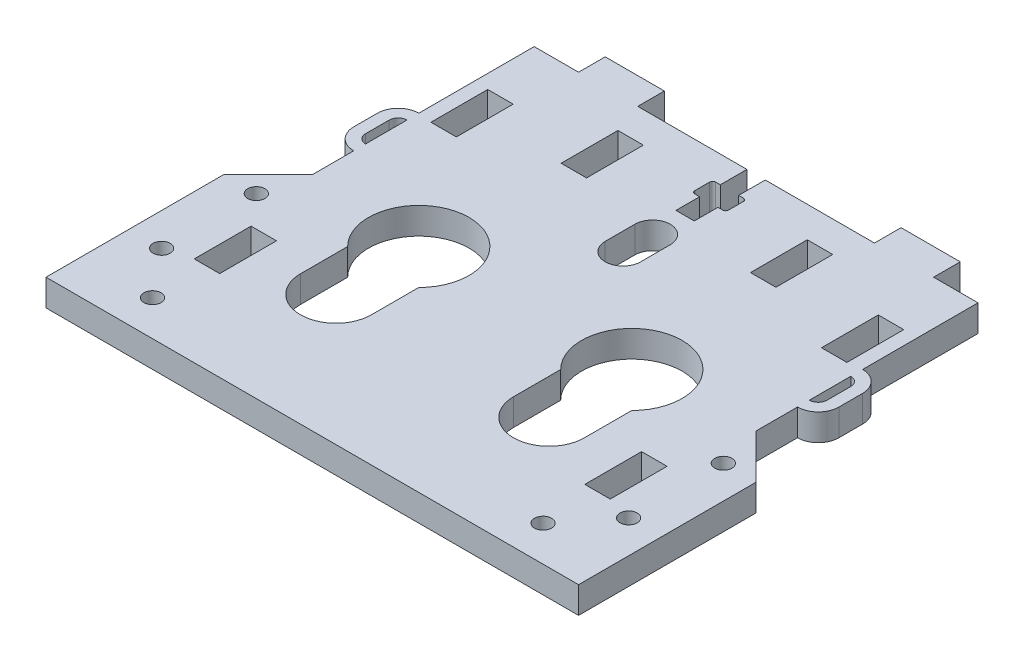
SolidWorks part; units mm, degrees
ref_plane "Front Plane" through (0, 0, 0) normal (0, 0, 1) x (1, 0, 0)
ref_plane "Top Plane" through (0, 0, 0) normal (0, 1, 0) x (1, 0, 0)
ref_plane "Right Plane" through (0, 0, 0) normal (1, 0, 0) x (0, 0, -1)
sketch "Sketch1" plane through (0, 0, 0) normal (0, 1, 0) x (1, 0, 0)
  line L1 (-37.5, 37.5) -> (37.5, 37.5)
  line L2 (-37.5, 37.5) -> (-37.5, -37.5)
  line L3 (-37.5, -37.5) -> (37.5, -37.5)
  line L4 (37.5, 37.5) -> (37.5, -37.5)
  line L5 (-37.5, 37.5) -> (37.5, -37.5) construction
  line L6 (-37.5, -37.5) -> (37.5, 37.5) construction
  point P0 (0, 0)
  dimension "D1" = 75
  dimension "D2" = 75
extrude "MainShape" add sketch "Sketch1" along normal blind 4.5
sketch "Sketch2" plane through (0, 4.5, 0) normal (0, 1, 0) x (1, 0, 0)
  line L0 (0, -37.5) -> (0, 37.5) construction
  line L1 (-37.5, -37.5) -> (37.5, -37.5) construction
  line L2 (37.5, 37.5) -> (-37.5, 37.5) construction
  line L4 (-5, 42) -> (5, 42)
  line L5 (-5, 42) -> (-5, 33)
  line L6 (-5, 33) -> (5, 33)
  line L7 (5, 42) -> (5, 33)
  line L8 (-5, 42) -> (5, 33) construction
  line L9 (-5, 33) -> (5, 42) construction
  dimension "D1" = 10
  dimension "D2" = 4.5
extrude "Tab1" [suppressed] add sketch "Sketch2" against normal through all
sketch "Sketch4" [suppressed] plane through (0, 4.5, 0) normal (0, 1, 0) x (1, 0, 0)
  line L0 (0, 42) -> (0, -37.5) construction
  line L1 (5, 42) -> (-5, 42) construction
  line L2 (-47.5, -37.5) -> (47.5, -37.5) construction
  line L3 (-40, 37.5) -> (-40, 27) construction
  line L4 (-5, 37.5) -> (-47.5, 37.5) construction
  line L5 (-38.25, 27) -> (-41.75, 27) construction
  line L6 (-41.75, 27) -> (-41.75, 37.5) construction
  line L7 (-38.25, 27) -> (-41.75, 27)
  line L8 (-41.75, 27) -> (-41.75, 29.5)
  line L9 (-41.75, 29.5) -> (-42.75, 29.5)
  line L10 (-43, 29.75) -> (-43, 33.45)
  line L11 (-42.75, 33.7) -> (-41.75, 33.7)
  line L12 (-41.75, 33.7) -> (-41.75, 37.5)
  line L13 (-41.75, 37.5) -> (-38.25, 37.5)
  line L14 (-38.25, 27) -> (-38.25, 37.5) construction
  line L15 (-38.25, 33.7) -> (-38.25, 37.5)
  line L16 (-37.25, 33.7) -> (-38.25, 33.7)
  line L17 (-37, 29.75) -> (-37, 33.45)
  line L18 (-38.25, 29.5) -> (-37.25, 29.5)
  line L19 (-38.25, 27) -> (-38.25, 29.5)
  line L20 (38.25, 27) -> (38.25, 37.5) construction
  line L21 (41.75, 27) -> (41.75, 37.5) construction
  line L22 (38.25, 27) -> (41.75, 27) construction
  line L23 (40, 37.5) -> (40, 27) construction
  line L24 (38.25, 27) -> (38.25, 29.5)
  line L25 (38.25, 29.5) -> (37.25, 29.5)
  line L26 (37, 29.75) -> (37, 33.45)
  line L27 (37.25, 33.7) -> (38.25, 33.7)
  line L28 (38.25, 33.7) -> (38.25, 37.5)
  line L29 (41.75, 37.5) -> (38.25, 37.5)
  line L30 (41.75, 33.7) -> (41.75, 37.5)
  line L31 (42.75, 33.7) -> (41.75, 33.7)
  line L32 (43, 29.75) -> (43, 33.45)
  line L33 (41.75, 29.5) -> (42.75, 29.5)
  line L34 (41.75, 27) -> (41.75, 29.5)
  line L35 (38.25, 27) -> (41.75, 27)
  arc A0 (-42.75, 29.5) -> (-43, 29.75) centre (-42.75, 29.75) cw
  arc A1 (-37, 29.75) -> (-37.25, 29.5) centre (-37.25, 29.75) cw
  arc A2 (-37.25, 33.7) -> (-37, 33.45) centre (-37.25, 33.45) cw
  arc A3 (-43, 33.45) -> (-42.75, 33.7) centre (-42.75, 33.45) cw
  arc A4 (43, 33.45) -> (42.75, 33.7) centre (42.75, 33.45) ccw
  arc A5 (37.25, 33.7) -> (37, 33.45) centre (37.25, 33.45) ccw
  arc A6 (37, 29.75) -> (37.25, 29.5) centre (37.25, 29.75) ccw
  arc A7 (42.75, 29.5) -> (43, 29.75) centre (42.75, 29.75) ccw
  point P24 (-43, 29.5)
  point P27 (-37, 29.5)
  point P30 (-37, 33.7)
  point P33 (-43, 33.7)
  point P56 (43, 33.7)
  point P57 (37, 33.7)
  point P58 (37, 29.5)
  point P59 (43, 29.5)
  dimension "D7" = 0.5
  dimension "D1" = 11
  dimension "D2" = 1.55
  dimension "D3" = 3.5
  dimension "D4" = 2.85
  dimension "D5" = 8
  dimension "D6" = 40
extrude "Cut-Extrude2" [suppressed] cut sketch "Sketch4" against normal through all
sketch "Sketch5" plane through (0, 4.5, 0) normal (0, 1, 0) x (1, 0, 0)
  line L0 (0, -37.5) -> (0, 37.5) construction
  line L1 (-37.5, -37.5) -> (37.5, -37.5) construction
  line L3 (33, 37.5) -> (33, -37.5) construction
  line L4 (37.5, 37.5) -> (-37.5, 37.5) construction
  line L5 (-33, 37.5) -> (-33, -37.5) construction
  line L6 (30.85, 27.3) -> (35.15, 27.3)
  line L7 (30.85, 27.3) -> (30.85, 17.7)
  line L8 (30.85, 17.7) -> (35.15, 17.7)
  line L9 (35.15, 27.3) -> (35.15, 17.7)
  line L10 (30.85, 27.3) -> (35.15, 17.7) construction
  line L11 (30.85, 17.7) -> (35.15, 27.3) construction
  line L12 (-30.85, 17.7) -> (-35.15, 27.3) construction
  line L13 (-30.85, 27.3) -> (-35.15, 17.7) construction
  line L14 (-35.15, 27.3) -> (-35.15, 17.7)
  line L15 (-30.85, 17.7) -> (-35.15, 17.7)
  line L16 (-30.85, 27.3) -> (-30.85, 17.7)
  line L17 (-30.85, 27.3) -> (-35.15, 27.3)
  line L18 (-37.5, 2.5) -> (37.5, 2.5) construction
  line L19 (-37.5, 37.5) -> (-37.5, -37.5) construction
  line L20 (37.5, -37.5) -> (37.5, 37.5) construction
  line L21 (-30.85, -22.3) -> (-35.15, -12.7) construction
  line L22 (-30.85, -12.7) -> (-35.15, -22.3) construction
  line L23 (30.85, -12.7) -> (35.15, -22.3) construction
  line L24 (30.85, -22.3) -> (35.15, -12.7) construction
  line L25 (-30.85, -22.3) -> (-35.15, -22.3)
  line L26 (-30.85, -22.3) -> (-30.85, -12.7)
  line L27 (-30.85, -12.7) -> (-35.15, -12.7)
  line L28 (-35.15, -22.3) -> (-35.15, -12.7)
  line L29 (35.15, -22.3) -> (35.15, -12.7)
  line L30 (30.85, -12.7) -> (35.15, -12.7)
  line L31 (30.85, -22.3) -> (30.85, -12.7)
  line L32 (30.85, -22.3) -> (35.15, -22.3)
  line L33 (-30.85, 27.3) -> (-35.15, 17.7) construction
  line L34 (-37.5, 37.5) -> (37.5, 37.5) construction
  line L35 (37.5, 37.5) -> (-37.5, 37.5) construction
  point P10 (33, 22.5)
  point P21 (-33, 22.5)
  point P36 (-33, -17.5)
  point P37 (33, -17.5)
  dimension "D1" = 33
  dimension "D2" = 9.6
  dimension "D3" = 4.3
  dimension "D4" = 15
  dimension "D5" = 40
extrude "Cut-Extrude3" cut sketch "Sketch5" against normal through all
sketch "Sketch6" plane through (0, 4.5, 0) normal (0, 1, 0) x (1, 0, 0)
  line L0 (-18, -37.5) -> (-18, 28) construction
  line L1 (-24, -15.5) -> (-24, -7.5208)
  line L3 (-37.5, -15.5) -> (37.5, -15.5) construction
  line L4 (-37.5, 37.5) -> (-37.5, -37.5) construction
  line L5 (37.5, -37.5) -> (37.5, 37.5) construction
  line L6 (37.5, 37.5) -> (-37.5, 37.5) construction
  line L7 (-37.5, -37.5) -> (37.5, -37.5) construction
  line L8 (-12, -15.5) -> (-12, -7.5208)
  line L9 (-37.5, 37.5) -> (37.5, 37.5) construction
  arc A0 (-24, -15.5) -> (-12, -15.5) centre (-18, -15.5) ccw
  arc A2 (-12, -7.5208) -> (-24, -7.5208) centre (-18, -1.5) ccw
  dimension "D1" = 12
  dimension "D6" = 8.5
  dimension "D2" = 53
  dimension "D3" = 0
  dimension "D5" = 0
  dimension "D7" = 14
  dimension "D4" = 18
extrude "Cut-Extrude4" cut sketch "Sketch6" against normal through all
sketch "Sketch13" plane through (0, 4.5, 0) normal (0, 1, 0) x (1, 0, 0)
  line L0 (-37.5, 0) -> (-45, -7.5)
  line L1 (-37.5, 37.5) -> (-37.5, -37.5) construction
  line L2 (-45, -7.5) -> (-45, -37.5)
  line L3 (-45, -37.5) -> (-37.5, -37.5)
  line L4 (-37.5, -37.5) -> (-37.5, 0)
  line L5 (0, 37.5) -> (0, -37.5) construction
  line L6 (37.5, 37.5) -> (-37.5, 37.5) construction
  line L7 (-37.5, -37.5) -> (37.5, -37.5) construction
  line L8 (37.5, -37.5) -> (37.5, 0)
  line L9 (45, -37.5) -> (37.5, -37.5)
  line L10 (45, -7.5) -> (45, -37.5)
  line L11 (37.5, 0) -> (45, -7.5)
  line L12 (-37.5, -37.5) -> (-37.5, 0)
  line M23 (37.5, -37.5) -> (37.5, 37.5)
  line M25 (-37.5, 37.5) -> (-37.5, -37.5)
  dimension "D1" = 45
  dimension "D2" = 30
extrude "Boss-Extrude2" add sketch "Sketch13" against normal through all contours L2 L3 L0 M25 | L11 L9 L10 M23 region at (-41.1111, 4.5, 20.5556) region at (41.1111, 4.5, 20.5556)
sketch "Sketch8" plane through (0, 4.5, 0) normal (0, 1, 0) x (1, 0, 0)
  line L0 (-18, -9.5) -> (-18, -21.5) construction
  line L1 (-18, -15.5) -> (-39.46, -15.5) construction
  line L2 (-39.46, -23.5) -> (-39.46, -7.5) construction
  line L3 (-18, -21.5) -> (-18, -9.5) construction
  circle A0 centre (-39.46, -7.5) radius 1.45
  circle A1 centre (-18, -15.5) radius 6 construction
  circle A2 centre (-39.46, -23.5) radius 1.45
  dimension "D3" = 2.9
  dimension "D1" = 0
  dimension "D2" = 8
  dimension "D4" = 21.46
extrude "Cut-Extrude6" cut sketch "Sketch8" against normal through all
mirror "Mirror1" about plane through (0, 0, 0) normal (1, 0, 0) of "Cut-Extrude6", "Cut-Extrude4"
sketch "Sketch11" plane through (0, 4.5, 0) normal (0, 1, 0) x (1, 0, 0)
  line L0 (0, 37.5) -> (0, -37.5) construction
  line L1 (37.5, 37.5) -> (-37.5, 37.5) construction
  line L2 (-45, -37.5) -> (45, -37.5) construction
  line L3 (-25, 42) -> (-25, 37.5) construction
  line L4 (-30, 37.5) -> (-20, 37.5)
  line L5 (-30, 37.5) -> (-30, 42)
  line L6 (-30, 42) -> (-20, 42)
  line L7 (-20, 37.5) -> (-20, 42)
  line L8 (25, 42) -> (25, 37.5) construction
  line L9 (20, 37.5) -> (20, 42)
  line L10 (30, 42) -> (20, 42)
  line L11 (30, 37.5) -> (30, 42)
  line L12 (30, 37.5) -> (20, 37.5)
  dimension "D1" = 10
  dimension "D2" = 4.5
  dimension "D3" = 25
extrude "RearTabs" add sketch "Sketch11" against normal through all
sketch "Sketch12" plane through (0, 4.5, 0) normal (0, 1, 0) x (1, 0, 0)
  line L0 (0, 0) -> (0, 37.5) construction
  line L1 (20, 37.5) -> (-20, 37.5) construction
  line L2 (1.55, 37.5) -> (-1.55, 37.5)
  line L3 (-1.55, 37.5) -> (-1.55, 33)
  line L4 (-1.55, 33) -> (-2.35, 33)
  line L5 (-2.85, 32.5) -> (-2.85, 30)
  line L6 (-2.35, 29.5) -> (-1.55, 29.5)
  line L7 (-1.55, 29.5) -> (-1.55, 25.5)
  line L8 (-1.55, 25.5) -> (1.55, 25.5)
  line L9 (1.55, 29.5) -> (1.55, 25.5)
  line L10 (2.35, 29.5) -> (1.55, 29.5)
  line L11 (2.85, 32.5) -> (2.85, 30)
  line L12 (1.55, 33) -> (2.35, 33)
  line L13 (1.55, 37.5) -> (1.55, 33)
  arc A0 (-2.85, 30) -> (-2.35, 29.5) centre (-2.35, 30) ccw
  arc A1 (-2.35, 33) -> (-2.85, 32.5) centre (-2.35, 32.5) ccw
  arc A2 (2.35, 33) -> (2.85, 32.5) centre (2.35, 32.5) cw
  arc A3 (2.85, 30) -> (2.35, 29.5) centre (2.35, 30) cw
  point P14 (-2.85, 29.5)
  point P17 (-2.85, 33)
  point P25 (0, 25.5)
  point P28 (2.85, 33)
  point P29 (2.85, 29.5)
  dimension "D5" = 8
  dimension "D1" = 12
  dimension "D6" = 0.5
  dimension "D2" = 3.5
  dimension "D3" = 2.85
  dimension "D4" = 1.55
extrude "FrontScrewSlot" cut sketch "Sketch12" against normal through all
sketch "Sketch14" plane through (0, 4.5, 0) normal (0, 1, 0) x (1, 0, 0)
  line L0 (-33, 27.3) -> (-33, -37.5) construction
  line L1 (-30.85, 27.3) -> (-35.15, 27.3) construction
  line L2 (-45, -37.5) -> (45, -37.5) construction
  line L3 (-30, 37.5) -> (-37.5, 37.5) construction
  line L4 (0, 0) -> (0, -37.5) construction
  line L5 (33, 27.3) -> (33, -37.5) construction
  line L6 (-33, 27.3) -> (-33, -37.5) construction
  circle A0 centre (-33, -31.5) radius 1.45
  circle A1 centre (33, -31.5) radius 1.45
  dimension "D2" = 2.9
  dimension "D1" = 69
extrude "BraceScrews" cut sketch "Sketch14" against normal through all
sketch "Sketch15" plane through (0, 4.5, 0) normal (0, 1, 0) x (1, 0, 0)
  line L0 (0, -37.5) -> (0, 25.5) construction
  line L1 (-45, -37.5) -> (45, -37.5) construction
  line L2 (-1.55, 25.5) -> (1.55, 25.5) construction
  line L3 (16, 27.5) -> (-16, 27.5) construction
  line L4 (-1.55, 37.5) -> (-20, 37.5) construction
  line L5 (-18.15, 32.3) -> (-13.85, 32.3)
  line L6 (-18.15, 32.3) -> (-18.15, 22.7)
  line L7 (-18.15, 22.7) -> (-13.85, 22.7)
  line L8 (-13.85, 32.3) -> (-13.85, 22.7)
  line L9 (-18.15, 32.3) -> (-13.85, 22.7) construction
  line L10 (-18.15, 22.7) -> (-13.85, 32.3) construction
  line L11 (18.15, 22.7) -> (13.85, 32.3) construction
  line L12 (18.15, 32.3) -> (13.85, 22.7) construction
  line L13 (13.85, 32.3) -> (13.85, 22.7)
  line L14 (18.15, 22.7) -> (13.85, 22.7)
  line L15 (18.15, 32.3) -> (18.15, 22.7)
  line L16 (18.15, 32.3) -> (13.85, 32.3)
  point P19 (0, 27.5)
  dimension "D1" = 16
  dimension "D2" = 4.3
  dimension "D3" = 9.6
  dimension "D4" = 10
extrude "FanTabs" cut sketch "Sketch15" against normal through all
sketch "Sketch16" plane through (0, 4.5, 0) normal (0, 1, 0) x (1, 0, 0)
  line L0 (0, 0) -> (0, 25.5) construction
  line L1 (-1.55, 25.5) -> (1.55, 25.5) construction
  line L2 (0, 20) -> (0, 15) construction
  line L3 (3, 20) -> (3, 15)
  line L4 (-3, 20) -> (-3, 15)
  arc A0 (3, 20) -> (-3, 20) centre (0, 20) ccw
  arc A1 (-3, 15) -> (3, 15) centre (0, 15) ccw
  point P7 (0, 17.5)
  dimension "D1" = 3
  dimension "D2" = 20
  dimension "D3" = 5
extrude "WiringSlot" cut sketch "Sketch16" against normal through all
sketch "Sketch17" plane through (0, 4.5, 0) normal (0, 1, 0) x (1, 0, 0)
  line L0 (-37.5, 14.5) -> (-37.5, 10.5) construction
  line L3 (-37.5, 37.5) -> (-37.5, 0) construction
  line L4 (-36, 14.5) -> (-36, 10.5)
  line L5 (-39, 14.5) -> (-39, 10.5)
  line L6 (-37.5, 14.5) -> (-37.5, 10.5) construction
  line L7 (-34, 14.5) -> (-34, 10.5)
  line L8 (-41, 14.5) -> (-41, 10.5)
  line L9 (-41, 12.5) -> (-37.5, 12.5) construction
  line L10 (0, 0) -> (0, -12.1805) construction
  arc A0 (-36, 14.5) -> (-39, 14.5) centre (-37.5, 14.5) ccw
  arc A1 (-39, 10.5) -> (-36, 10.5) centre (-37.5, 10.5) ccw
  arc A2 (-34, 14.5) -> (-41, 14.5) centre (-37.5, 14.5) ccw
  arc A3 (-41, 10.5) -> (-34, 10.5) centre (-37.5, 10.5) ccw
  point P4 (-37.5, 12.5)
  point P10 (-37.5, 12.5)
  dimension "D4" = 4
  dimension "D5" = 25
  dimension "D1" = 0
  dimension "D2" = 2
  dimension "D3" = 1.5
extrude "Boss-Extrude3" add sketch "Sketch17" against normal through all
mirror "Mirror2" about plane through (0, 0, 0) normal (1, 0, 0) of "Boss-Extrude3"
equation "\"X-ROD-SPACING\"=45"
equation "\"Y-ROD-SPACING\"=75"
equation "\"Z-ROD-SPACING\"=17.5"
equation "\"Y-BED-OFFSET\"=2"
equation "\"Y-BED-ROD-INSET\"=3.5"
equation "\"Y-BED-SCREW-SPACING\"=209"
equation "\"Y-BED-SCREW-CUTOUT-SLOT-HEIGHT\"=2"
equation "\"T-SLOT-NUT-FILLET-RADIUS\"=0.5"
equation "\"T-SLOT-SCREW-SHAFT-RADIUS\"=1.55"
equation "\"T-SLOT-SCREW-SHAFT-CUTOUT-LENGTH\"=11.0"
equation "\"T-SLOT-NUT-DEPTH\"=3.5"
equation "\"T-SLOT-NUT-WIDTH\"=2.85"
equation "\"T-SLOT-NUT-END-DISTANCE\"=8"
equation "\"ACRYLIC-THICKNESS\"=10"
equation "\"ACRYLIC-THICKNESS2\"=4.5"
equation "\"ACRYLIC-TAB-CUTOUT-SIZE\"=\"ACRYLIC-THICKNESS\"+\"ACRYLIC-TAB-TOLERANCE\"*2"
equation "\"ACRYLIC-TAB-WIDTH\"=\"ACRYLIC-THICKNESS\""
equation "\"ACRYLIC-M3-HOLE\"=2.9"
equation "\"SMOOTHROD-CAP-SCREW-DISTANCE\"=20"
equation "\"FRAME-WIDTH-INNER\"=370"
equation "\"NEMA17-HOLE-SPACING\"=31"
equation "\"NEMA17-CENTRAL-CUTOUT\"=22.5"
equation "\"Z-BRACKET-REACH\"=55"
equation "\"Z-ROD-INSET\"=16"
equation "\"TOP-BRACKET-SPACING\"=40"
equation "\"SMOOTHROD-X-LENGTH\"=350"
equation "\"SMOOTHROD-Y-LENGTH\"=350"
equation "\"SMOOTHROD-Z-LENGTH\"=350"
equation "\"SMOOTHROD-TIGHTENING-HEADROOM\"=.25"
equation "\"LEADSCREW-Z-LENGTH\"=300"
equation "\"SCREW-LENGTH-FRAME\"=\"ACRYLIC-THICKNESS\" + 10"
equation "\"SCREW-LENGTH-MOTOR\"=\"ACRYLIC-THICKNESS\" + 5"
equation "\"SCREW-LENGTH-EXTRUDER\"=28"
equation "\"SCREW-HEAD-RADIUS\"=6"
equation "\"PRINTED-X-SMOOTHROD-DIAMETER\"=9.0"
equation "\"PRINTED-X-SMOOTHROD-CUTOUT\"=10"
equation "\"PRINTED-X-BASE-HEIGHT\"=10"
equation "\"PRINTED-LM8UU-CUTOUT-SIZE\"=15.5"
equation "\"PRINTED-LM8UU-CUTOUT-LENGTH\"=24.5"
equation "\"PRINTED-X-IDLER-HEIGHT\"=16"
equation "\"PSU-MOUNTING-WIDTH\"=95"
equation "\"PSU-MOUNTING-HEIGHT\"=177"
equation "\"Y-BELT-TO-ROD-DISTANCE\"=20"
equation "\"SPOOL-HOLDER-ROD-SPACING\"=150"
equation "\"ACRYLIC-X-CARRIAGE-WIDTH\"=55"
equation "\"ACRYLIC-X-CARRIAGE-HEIGHT\"=75"
equation "\"ACRYLIC-X-CARRIAGE-SCREW-SPACING-X\"=15"
equation "\"ACRYLIC-X-CARRIAGE-SCREW-SPACING-Y\"=33"
equation "\"ACRYLIC-X-CARRIAGE-CENTER-TAB-SPACING\"=14"
equation "\"D1@MainShape\" = \"ACRYLIC-THICKNESS2\""
equation "\"D1@Sketch2\"=\"ACRYLIC-TAB-WIDTH\""
equation "\"D2@Sketch2\"=\"ACRYLIC-THICKNESS2\""
equation "\"D1@Sketch4\"=\"T-SLOT-SCREW-SHAFT-CUTOUT-LENGTH\""
equation "\"D2@Sketch4\"=\"T-SLOT-SCREW-SHAFT-RADIUS\""
equation "\"D3@Sketch4\"=\"T-SLOT-NUT-DEPTH\""
equation "\"D4@Sketch4\"=\"T-SLOT-NUT-WIDTH\""
equation "\"D5@Sketch4\"=\"T-SLOT-NUT-END-DISTANCE\""
equation "\"D7@Sketch4\"=\"T-SLOT-NUT-FILLET-RADIUS\""
equation "\"ACRYLIC-X-CARRIAGE-EXTRUDER-SHELF-DEPTH\"=\"ACRYLIC-X-CARRIAGE-EXTRUDER-OFFSET\" + 28"
equation "\"ACRYLIC-X-CARRIAGE-LM8UU-CUTOUT-WIDTH\"=24.25"
equation "\"ACRYLIC-X-CARRIAGE-EXTRUDER-BRACE-SPACING\"=23"
equation "\"ACRYLIC-X-CARRIAGE-EXTRUDER-BRACE-TAB-OFFSET\"=20"
equation "\"ACRYLIC-X-CARRIAGE-EXTRUDER-BRACE-HEIGHT\"=35"
equation "\"ACRYLIC-X-CARRIAGE-EXTRUDER-BRACE-SCREW-SPACING\"=22"
equation "\"D2@Sketch5\"=\"ACRYLIC-THICKNESS2-TAB-CUTOUT-HEIGHT\""
equation "\"D3@Sketch5\"=\"ACRYLIC-THICKNESS2-TAB-CUTOUT-WIDTH\""
equation "\"D3@Sketch8\"=\"ACRYLIC-M3-HOLE\""
equation "\"ACRYLIC-X-CARRIAGE-EXTRUDER-ANGLE\"=90"
equation "\"ACRYLIC-X-CARRIAGE-EXTRUDER-OFFSET\"=26"
equation "\"ACRYLIC-TAB-TOLERANCE\"=-.05"
equation "\"ACRYLIC-X-CARRIAGE-DUAL-WIDTH-MULTIPLIER\"=1.65"
equation "\"ACRYLIC-X-CARRIAGE-DUAL-HOTEND-SPACING\"=42"
equation "\"ACRYLIC-X-CARRIAGE-DUAL-WIDTH\"=75"
equation "\"ACRYLIC-X-CARRIAGE-DUAL-HOTEND-SEPARATION\"=36"
equation "\"ACRYLIC-X-CARRIAGE-DUAL-MOUNT-PLATE-DEPTH\"=75"
equation "\"ACRYLIC-X-CARRIAGE-DUAL-MOUNT-BRACE-WIDTH\"=33"
equation "\"D1@Sketch5\"=\"ACRYLIC-X-CARRIAGE-DUAL-MOUNT-BRACE-WIDTH\""
equation "\"ACRYLIC-X-CARRIAGE-DUAL-MOUNT-SCREW-WIDTH\"=40"
equation "\"D6@Sketch4\"=\"ACRYLIC-X-CARRIAGE-DUAL-MOUNT-SCREW-WIDTH\""
equation "\"D1@Sketch1\"=\"ACRYLIC-X-CARRIAGE-DUAL-WIDTH\""
equation "\"D2@Sketch1\"=\"ACRYLIC-X-CARRIAGE-DUAL-MOUNT-PLATE-DEPTH\""
equation "\"D4@Sketch6\"=\"ACRYLIC-X-CARRIAGE-DUAL-HOTEND-SEPARATION\"/2"
equation "\"D1@Sketch11\"=\"ACRYLIC-TAB-WIDTH\""
equation "\"D2@Sketch11\"=\"ACRYLIC-THICKNESS2\""
equation "\"D1@Sketch12\"=\"T-SLOT-SCREW-SHAFT-CUTOUT-LENGTH\"+1"
equation "\"D2@Sketch12\"=\"T-SLOT-NUT-DEPTH\""
equation "\"D3@Sketch12\"=\"T-SLOT-NUT-WIDTH\""
equation "\"D4@Sketch12\"=\"T-SLOT-SCREW-SHAFT-RADIUS\""
equation "\"D5@Sketch12\"=\"T-SLOT-NUT-END-DISTANCE\""
equation "\"D6@Sketch12\"=\"T-SLOT-NUT-FILLET-RADIUS\""
equation "\"D2@Sketch14\"=\"ACRYLIC-M3-HOLE\""
equation "\"D2@Sketch15\"=\"ACRYLIC-THICKNESS2-TAB-CUTOUT-WIDTH\""
equation "\"D3@Sketch15\"=\"ACRYLIC-THICKNESS2-TAB-CUTOUT-HEIGHT\""
equation "\"KERF\"=0.1"
equation "\"PRINTED-M3-HOLE\"=3.5"
equation "\"PRINTED-M3-NUT-AF\"=6.25"
equation "\"ACRYLIC-X-CARRIAGE-LM8UU-CUTOUT-HEIGHT\"=11.0"
equation "\"ACRYLIC-X-CARRIAGE-DUAL-FAN-OFFSET\"=52"
equation "\"ACRYLIC-X-CARRIAGE-DUAL-FAN-HEIGHT\"=20"
equation "\"BLOWER-FAN-WIDTH\"=15"
equation "\"ACRYLIC-THICKNESS-TAB-CUTOUT-WIDTH\"=\"ACRYLIC-THICKNESS\"-\"KERF\"*2"
equation "\"ACRYLIC-THICKNESS-TAB-CUTOUT-HEIGHT\"=\"ACRYLIC-TAB-WIDTH\"-\"KERF\"*4"
equation "\"ACRYLIC-THICKNESS2-TAB-CUTOUT-WIDTH\"=\"ACRYLIC-THICKNESS2\"-\"KERF\"*2"
equation "\"ACRYLIC-THICKNESS2-TAB-CUTOUT-HEIGHT\"=\"ACRYLIC-TAB-WIDTH\"-\"KERF\"*4"
